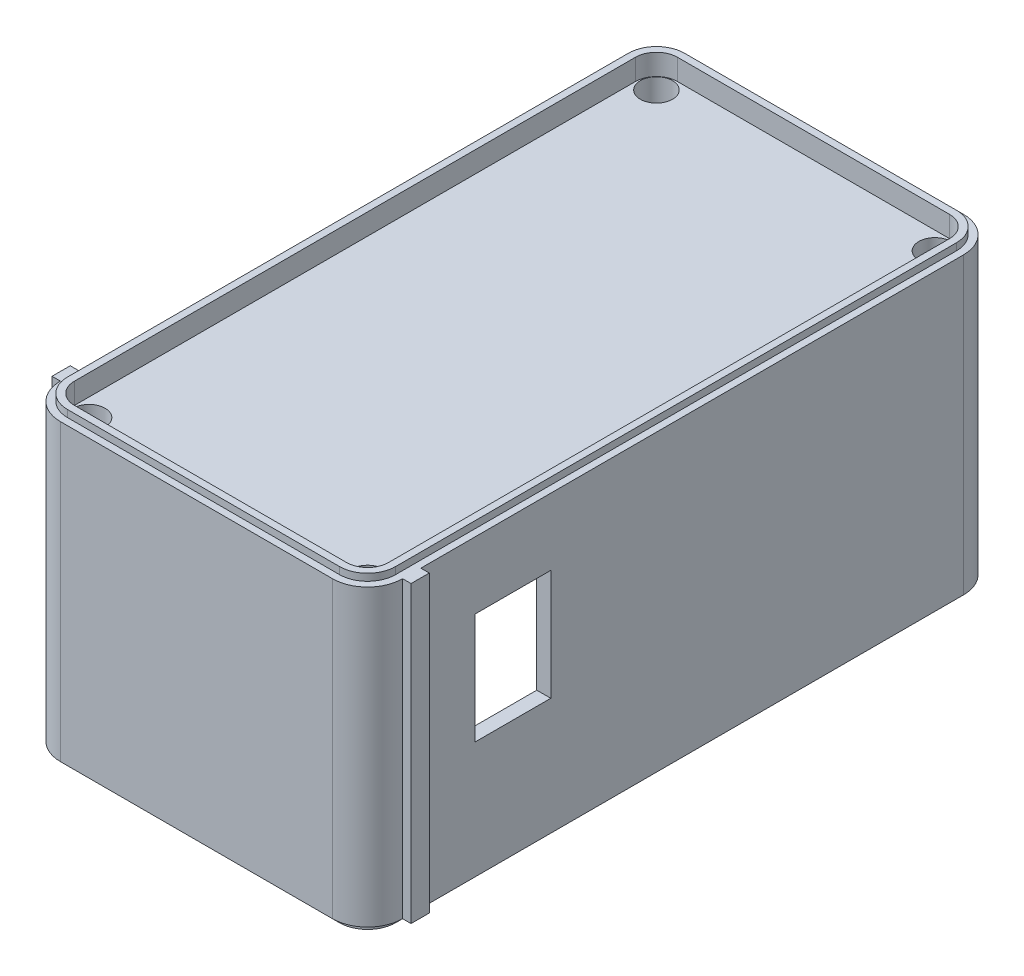
SolidWorks part; units mm, degrees
note: The reader was unsure of these and kept them because the rebuilt part matched: shared geometry of "Croquis1<6>", "Croquis1<4>", "Croquis5<3>", "Croquis5<4>", "Croquis5<6>", "Croquis5<7>".
material "ABS PC"
ref_plane "Alzado" through (0, 0, 0) normal (0, 0, 1) x (1, 0, 0)
ref_plane "Planta" through (0, 0, 0) normal (0, 1, 0) x (1, 0, 0)
ref_plane "Vista lateral" through (0, 0, 0) normal (1, 0, 0) x (0, 0, -1)
sketch "Croquis1" plane through (0, 0, 0) normal (0, 1, 0) x (1, 0, 0)
  line L0 (0, 22.5) -> (0, -22.5) construction
  line L1 (-9.7, 22.5) -> (9.7, 22.5)
  line L2 (-12.2, 20) -> (-12.2, -20)
  line L3 (-9.7, -22.5) -> (9.7, -22.5)
  line L4 (12.2, 20) -> (12.2, -20)
  line L5 (-12.2, 0) -> (12.2, 0) construction
  line L6 (-9.7, 21.5) -> (9.7, 21.5)
  line L7 (11.2, 20) -> (11.2, -20)
  line L8 (-9.7, -21.5) -> (9.7, -21.5)
  line L9 (-11.2, 20) -> (-11.2, -20)
  line L10 (-11.7, 20) -> (-11.7, -20)
  line L11 (-9.7, -22) -> (9.7, -22)
  line L12 (11.7, 20) -> (11.7, -20)
  line L13 (-9.7, 22) -> (9.7, 22)
  arc A0 (9.7, -22.5) -> (12.2, -20) centre (9.7, -20) ccw
  arc A1 (-12.2, -20) -> (-9.7, -22.5) centre (-9.7, -20) ccw
  arc A2 (-9.7, 22.5) -> (-12.2, 20) centre (-9.7, 20) ccw
  arc A3 (9.7, 22.5) -> (12.2, 20) centre (9.7, 20) cw
  arc A4 (9.7, 21.5) -> (11.2, 20) centre (9.7, 20) cw
  arc A5 (9.7, -21.5) -> (11.2, -20) centre (9.7, -20) ccw
  arc A6 (-11.2, -20) -> (-9.7, -21.5) centre (-9.7, -20) ccw
  arc A7 (-9.7, 21.5) -> (-11.2, 20) centre (-9.7, 20) ccw
  arc A8 (-9.7, 22) -> (-11.7, 20) centre (-9.7, 20) ccw
  arc A9 (-11.7, -20) -> (-9.7, -22) centre (-9.7, -20) ccw
  arc A10 (9.7, -22) -> (11.7, -20) centre (9.7, -20) ccw
  arc A11 (9.7, 22) -> (11.7, 20) centre (9.7, 20) cw
  circle A12 centre (-9.93, 20.23) radius 1.15
  circle A13 centre (9.93, 20.23) radius 1.15
  circle A14 centre (9.93, -20.23) radius 1.15
  circle A15 centre (-9.93, -20.23) radius 1.15
  point P8 (0, 0)
  point P14 (-12.2, -22.5)
  point P17 (-12.2, 22.5)
  point P20 (12.2, 22.5)
  dimension "D3" = 2.5
  dimension "D5" = 0.5
  dimension "D6" = 2.3
  dimension "D1" = 24.4
  dimension "D2" = 45
  dimension "D7" = 2.27
  dimension "D8" = 2.27
  dimension "D4" = 1
extrude "Saliente-Extruir1" add sketch "Croquis1" along normal mid plane 21 contours L3 A0 L4 A3 L1 A2 L2 A1
extrude "Cortar-Extruir2" cut sketch "Croquis1<6>" against normal up to next and the other way up to next contours A12 | A13 | A15 | A14
sketch "Croquis1<6>" plane through (0, 0, 0) normal (0, 1, 0) x (1, 0, 0) same geometry as "Croquis1"
shell "Vaciado3" thickness 1
extrude "Saliente-Extruir2" add sketch "Croquis1<4>" along normal blind 0.5 from offset 10.5 contours A11 L13 A8 L10 A9 L11 A10 L12 A7 L6 A4 L7 A5 L8 A6 L9
sketch "Croquis1<4>" plane through (0, 0, 0) normal (0, 1, 0) x (1, 0, 0) same geometry as "Croquis1"
mirror "Simetría3" about plane through (0, 0, 0) normal (0, 1, 0) of "Saliente-Extruir2"
sketch "Croquis4" plane through (0, 10.5, 0) normal (0, 1, 0) x (1, 0, 0)
  line L0 (-9.7, -22) -> (9.7, -22) construction
  line L1 (11.7, 20) -> (11.7, -20) construction
  line L4 (-8.2, 20.5) -> (-8.2, 20)
  line L5 (-9.7, 18.5) -> (-10.2, 18.5)
  line L6 (0, 0) -> (0, 20.5) construction
  line L7 (0, 0) -> (10.2, 0) construction
  line L9 (-10.2, 18.5) -> (-10.2, -18.5)
  line L11 (-8.2, -20.5) -> (8.2, -20.5)
  line L13 (10.2, -18.5) -> (10.2, 18.5)
  line L15 (8.2, 20.5) -> (-8.2, 20.5)
  line L16 (9.7, 18.5) -> (10.2, 18.5)
  line L17 (8.2, 20.5) -> (8.2, 20)
  line L18 (9.7, -18.5) -> (10.2, -18.5)
  line L19 (8.2, -20.5) -> (8.2, -20)
  line L20 (-9.7, -18.5) -> (-10.2, -18.5)
  line L21 (-8.2, -20.5) -> (-8.2, -20)
  arc A4 (-8.2, 20) -> (-9.7, 18.5) centre (-9.7, 20) cw
  arc A5 (8.2, 20) -> (9.7, 18.5) centre (9.7, 20) ccw
  arc A6 (8.2, -20) -> (9.7, -18.5) centre (9.7, -20) cw
  arc A7 (-8.2, -20) -> (-9.7, -18.5) centre (-9.7, -20) ccw
  dimension "D3" = 1.5
  dimension "D2" = 0.5
  dimension "D1" = 1.5
  dimension "D4" = 1.5
extrude "Cortar-Extruir3" cut sketch "Croquis4" against normal blind 1
sketch "Croquis5" plane through (-12.2, 0, 0) normal (-1, 0, 0) x (0, 0, 1)
  line L0 (-1.7, -1.3) -> (-8.1, -1.3)
  line L1 (-0.9, -5.5) -> (-8.9, -5.5)
  line L2 (-0.9, -5.5) -> (-0.9, -0.5)
  line L3 (-0.9, -0.5) -> (-8.9, -0.5)
  line L4 (-8.9, -5.5) -> (-8.9, -0.5)
  line L5 (-8.1, -4.7) -> (-8.1, -1.3)
  line L6 (-1.7, -4.7) -> (-8.1, -4.7)
  line L7 (-1.7, -4.7) -> (-1.7, -1.3)
  line L8 (-1.8, -1.4) -> (-8, -1.4)
  line L9 (-8, -4.6) -> (-8, -1.4)
  line L10 (-1.8, -4.6) -> (-8, -4.6)
  line L11 (-1.8, -4.6) -> (-1.8, -1.4)
  line L12 (-2.1, -1.7) -> (-7.7, -1.7)
  line L13 (-7.7, -4.3) -> (-7.7, -1.7)
  line L14 (-2.1, -4.3) -> (-7.7, -4.3)
  line L15 (-2.1, -4.3) -> (-2.1, -1.7)
  line L16 (-20, -10.5) -> (20, -10.5) construction
  line L17 (12.1353, 6.732) -> (12.1353, 5.732) construction
  line L18 (6.1353, -8.268) -> (18.1353, -8.268)
  line L19 (6.1353, -8.268) -> (6.1353, 6.732)
  line L20 (6.1353, 6.732) -> (18.1353, 6.732)
  line L21 (18.1353, -8.268) -> (18.1353, 6.732)
  line L22 (9.4353, 5.732) -> (14.8353, 5.732)
  line L23 (9.4353, 5.732) -> (9.4353, -2.168)
  line L24 (9.4353, -2.168) -> (14.8353, -2.168)
  line L25 (14.8353, 5.732) -> (14.8353, -2.168)
  line L26 (6.6353, 2.332) -> (8.6353, 2.332)
  line L27 (6.6353, 5.732) -> (8.6353, 5.732)
  line L28 (6.6353, 5.732) -> (6.6353, 4.532)
  line L29 (6.6353, 4.532) -> (8.6353, 4.532)
  line L30 (8.6353, 5.732) -> (8.6353, 4.532)
  line L31 (6.6353, 3.532) -> (8.6353, 3.532)
  line L32 (6.6353, 3.532) -> (6.6353, 2.332)
  line L33 (8.6353, 3.532) -> (8.6353, 2.332)
  line L34 (6.6353, 0.132) -> (8.6353, 0.132)
  line L35 (6.6353, 1.332) -> (8.6353, 1.332)
  line L36 (6.6353, 1.332) -> (6.6353, 0.132)
  line L37 (8.6353, 1.332) -> (8.6353, 0.132)
  line L38 (6.6353, -2.068) -> (8.6353, -2.068)
  line L39 (6.6353, -0.868) -> (8.6353, -0.868)
  line L40 (6.6353, -0.868) -> (6.6353, -2.068)
  line L41 (8.6353, -0.868) -> (8.6353, -2.068)
  line L42 (6.6353, 4.532) -> (6.6353, 2.332) construction
  line L43 (17.6353, 4.532) -> (17.6353, 2.332) construction
  line L44 (15.6353, -0.868) -> (15.6353, -2.068)
  line L45 (17.6353, -0.868) -> (17.6353, -2.068)
  line L46 (17.6353, -0.868) -> (15.6353, -0.868)
  line L47 (17.6353, -2.068) -> (15.6353, -2.068)
  line L48 (15.6353, 1.332) -> (15.6353, 0.132)
  line L49 (17.6353, 1.332) -> (17.6353, 0.132)
  line L50 (17.6353, 1.332) -> (15.6353, 1.332)
  line L51 (17.6353, 0.132) -> (15.6353, 0.132)
  line L52 (15.6353, 3.532) -> (15.6353, 2.332)
  line L53 (17.6353, 3.532) -> (17.6353, 2.332)
  line L54 (17.6353, 3.532) -> (15.6353, 3.532)
  line L55 (15.6353, 5.732) -> (15.6353, 4.532)
  line L56 (17.6353, 4.532) -> (15.6353, 4.532)
  line L57 (17.6353, 5.732) -> (17.6353, 4.532)
  line L58 (17.6353, 5.732) -> (15.6353, 5.732)
  line L59 (17.6353, 2.332) -> (15.6353, 2.332)
  line L60 (-6.9, -3) -> (-4.9, -3) construction
  line L62 (20, 10.5) -> (18.7, 10.5)
  line L63 (20, 10.5) -> (20, -12.5174)
  line L64 (20, -12.5174) -> (18.7, -12.5174)
  line L65 (18.7, 10.5) -> (18.7, -12.5174)
  circle A0 centre (-6.9, -3) radius 0.3
  circle A1 centre (-4.9, -3) radius 0.3
  circle A2 centre (-2.9, -3) radius 0.3
  point P27 (12.1353, 6.732)
  point P67 (-7.7, -3)
  line M1 (-20, -10.5) -> (20, -10.5)
  line M2 (20, -10.5) -> (20, 10.5)
  line M3 (20, 10.5) -> (-20, 10.5)
  dimension "D20" = 0.6
  dimension "D1" = 8
  dimension "D2" = 5
  dimension "D6" = 5
  dimension "D7" = 0.9
  dimension "D8" = 12
  dimension "D9" = 15
  dimension "D10" = 7.9
  dimension "D11" = 5.4
  dimension "D12" = 1
  dimension "D14" = 2.2
  dimension "D15" = 1
  dimension "D16" = 2
  dimension "D17" = 1.2
  dimension "D19" = 2
  dimension "D21" = 0.8
  dimension "D22" = 0.8
  dimension "D23" = 1.3
  dimension "D24" = 0.8
  dimension "D3" = 0.8
  dimension "D4" = 0.1
  dimension "D5" = 0.3
  dimension "D13" = 4
  dimension "D18" = 3
extrude "Cortar-Extruir4" cut sketch "Croquis5" against normal blind 0.8 contours L5 L0 L7 L6
chamfer "Chaflán2" distance 0.5 angle 45 4 edges at (-12.2, -4.7, -4.9) (-12.2, -3, -1.7) (-12.2, -1.3, -4.9) (-12.2, -3, -8.1)
extrude "Saliente-Extruir3" add sketch "Croquis5<3>" along normal blind 1.5 from surface at -0.8 separate body contours L10 L11 L8 L9 L15 L14 L13 L12 starting at face at (-11.4, -3, -4.9)
sketch "Croquis5<3>" plane through (-12.2, 0, 0) normal (-1, 0, 0) x (0, 0, 1) same geometry as "Croquis5"
extrude "Cortar-Extruir5" cut sketch "Croquis5<4>" against normal through all contours L25 L22 L23 L24
sketch "Croquis5<4>" plane through (-12.2, 0, 0) normal (-1, 0, 0) x (0, 0, 1) same geometry as "Croquis5"
extrude "Saliente-Extruir4" add sketch "Croquis5<6>" along normal blind 1.4 from surface at -0.8 contours A0 | A1 | A2 starting at face at (-11.4, -3, -4.9)
sketch "Croquis5<6>" plane through (-12.2, 0, 0) normal (-1, 0, 0) x (0, 0, 1) same geometry as "Croquis5"
extrude "Saliente-Extruir5" add sketch "Croquis5<7>" along normal blind 0.6 contours L65 M3 M1 M2
sketch "Croquis5<7>" plane through (-12.2, 0, 0) normal (-1, 0, 0) x (0, 0, 1) same geometry as "Croquis5"
mirror "Simetría4" about plane through (0, 0, 0) normal (1, 0, 0) of "Saliente-Extruir5"
